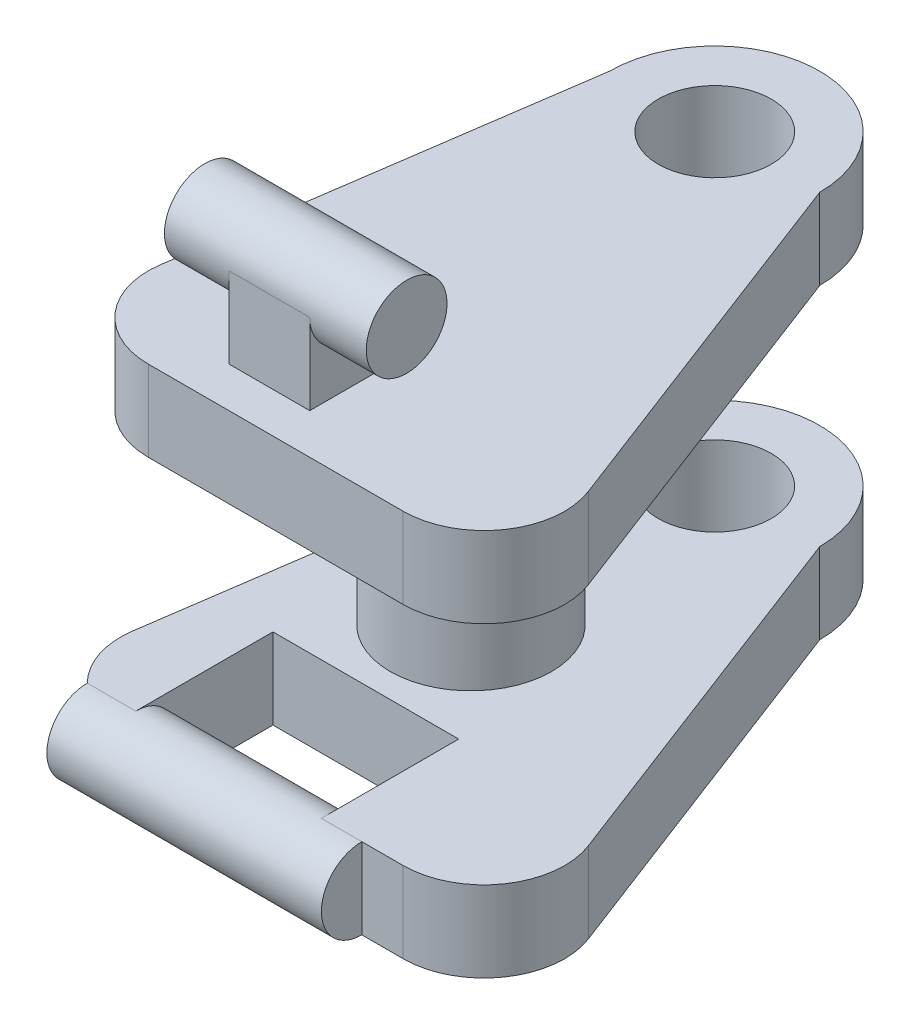
SolidWorks part; units mm, degrees
material "Alloy Steel (SS)"
ref_plane "Front Plane" through (0, 0, 0) normal (0, 0, 1) x (1, 0, 0)
ref_plane "Top Plane" through (0, 0, 0) normal (0, 1, 0) x (1, 0, 0)
ref_plane "Right Plane" through (0, 0, 0) normal (1, 0, 0) x (0, 0, -1)
sketch "Sketch1" plane through (0, 0, 0) normal (0, 1, 0) x (1, 0, 0)
  line L1 (3.2476, 60) -> (-5.4629, 0)
  line L2 (-5.4629, 0) -> (52.204, 0)
  line L5 (29.2476, 60) -> (52.204, 0)
  circle A0 centre (16.2476, 60) radius 7
  circle A1 centre (16.2476, 60) radius 13
  point P0 (51.702, 0)
extrude "Boss-Extrude2" add sketch "Sketch1" along normal blind 10 contours A1 L1 L2 L5 | A1 A0 region at (20.7328, 0, -22.8719) region at (16.2476, 0, -72.6323)
sketch "Sketch2" plane through (0, 0, 0) normal (0, -1, 0) x (1, 0, 0)
  circle A0 centre (16.0525, -30) radius 10
extrude "Boss-Extrude3" add sketch "Sketch2" along normal blind 28
sketch "Sketch3" plane through (0, -28, 0) normal (0, -1, 0) x (1, 0, 0)
  line L0 (3.2476, -60) -> (-5.4629, 0)
  line L1 (-5.4629, 0) -> (52.204, 0)
  line L2 (52.204, 0) -> (29.2476, -60)
  circle A0 centre (16.2476, -60) radius 7
  circle A1 centre (16.2476, -60) radius 13
  circle M1 centre (16.0525, -30) radius 10
extrude "Boss-Extrude4" add sketch "Sketch3" along normal blind 10 separate body contours A1 L2 L1 L0 M1 | A1 A0 region at (-0.2841, -28, -29.8804) region at (16.2476, -28, -47.3677)
fillet "Fillet2" radius 10 2 edges at (52.204, 5, 0) (-5.4629, 5, 0)
sketch "Sketch4" plane through (0, 0, 0) normal (0, 0, 1) x (1, 0, 0)
  line L0 (-5.4629, -33) -> (4.5371, -33)
  line L1 (-5.4629, -38) -> (-5.4629, -28) construction
  line L2 (4.5371, -38) -> (4.5371, -28)
  line L3 (-5.4629, -28) -> (52.204, -28) construction
  line L4 (4.5371, -28) -> (27.5371, -28)
  line L5 (27.5371, -28) -> (27.5371, -38)
  line L6 (-5.4629, -38) -> (52.204, -38) construction
  line L7 (27.5371, -38) -> (4.5371, -38)
  point P4 (4.6561, -38)
  line M3 (52.204, -28) -> (-5.4629, -28)
  line M5 (-5.4629, -38) -> (52.204, -38)
extrude "Cut-Extrude1" cut sketch "Sketch4" against normal blind 17 contours L5 L2 M3 M5 region at (16.0371, -33, 0)
sketch "Sketch5" plane through (27.5371, 0, 0) normal (-1, 0, 0) x (0, 0, 1)
  line L0 (0, -38) -> (0, -28) construction
  circle A0 centre (0, -33) radius 5
extrude "Boss-Extrude5" add sketch "Sketch5" along normal blind 29 and the other way blind 5
fillet "Fillet3" radius 10 2 edges at (52.204, -33, 0) (-5.4629, -33, 0)
sketch "Sketch6" plane through (0, -28, 0) normal (0, -1, 0) x (1, 0, 0)
  circle A0 centre (16.0525, -30) radius 10
extrude "Boss-Extrude6" add sketch "Sketch6" along normal up to vertex (10 mm away) up to point (29.2476, -38, -60)
sketch "Sketch7" plane through (0, 10, 0) normal (0, 1, 0) x (1, 0, 0)
  line L0 (16.0936, 0) -> (16.0936, 10)
  line L1 (6.0936, 0) -> (37.671, 0) construction
  line L2 (6.0936, 0) -> (16.0936, 0)
  line L3 (11.0936, 5) -> (21.0936, 5)
  line L4 (11.0936, 5) -> (11.0936, 15)
  line L5 (11.0936, 15) -> (21.0936, 15)
  line L6 (21.0936, 5) -> (21.0936, 15)
  line L7 (11.0936, 5) -> (21.0936, 15) construction
  line L8 (11.0936, 15) -> (21.0936, 5) construction
extrude "Boss-Extrude7" add sketch "Sketch7" along normal blind 10 contours L3 L6 L5 L4 region at (11.2351, 10, -10)
sketch "Sketch8" plane through (11.0936, 0, 0) normal (-1, 0, 0) x (0, 0, 1)
  line L0 (-5, 20) -> (-15, 20) construction
  circle A0 centre (-10, 20) radius 5
extrude "Boss-Extrude8" add sketch "Sketch8" along normal blind 8 and the other way blind 17
